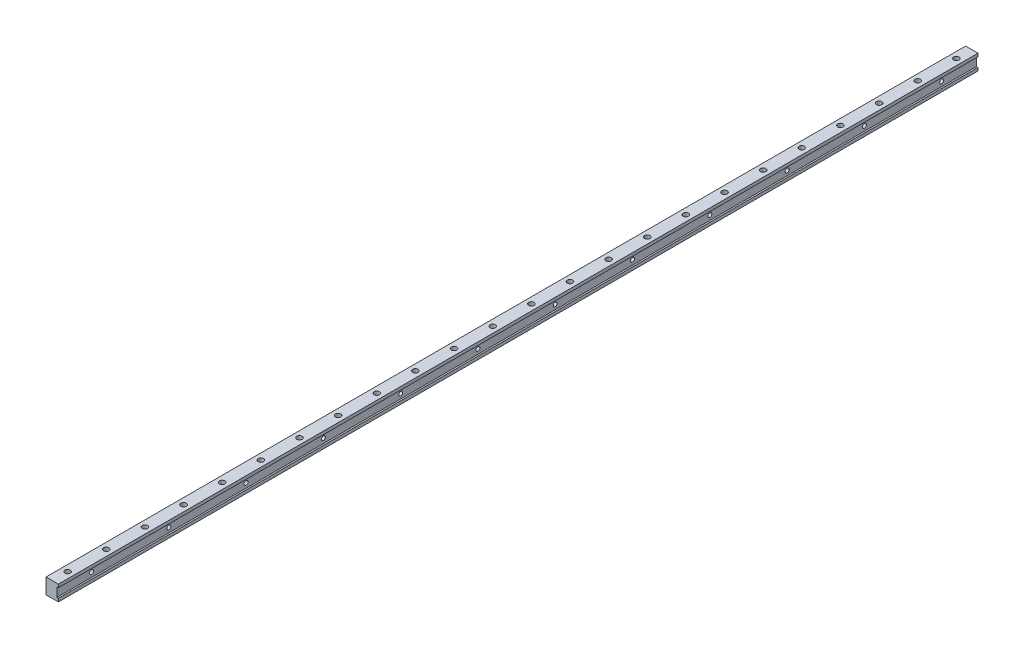
SolidWorks part; units mm, degrees
ref_plane "Front Plane" through (0, 0, 0) normal (0, 0, 1) x (1, 0, 0)
ref_plane "Top Plane" through (0, 0, 0) normal (0, 1, 0) x (1, 0, 0)
ref_plane "Right Plane" through (0, 0, 0) normal (1, 0, 0) x (0, 0, -1)
sketch "Sketch1" plane through (0, 0, 0) normal (0, 0, 1) x (1, 0, 0)
  line L1 (-4, -5) -> (4, -5)
  line L2 (-4, -5) -> (-4, 5)
  line L3 (-4, 5) -> (4, 5)
  line L4 (4, -5) -> (4, 5)
  line L5 (-4, -5) -> (4, 5) construction
  line L6 (-4, 5) -> (4, -5) construction
  point P0 (0, 0)
  dimension "D1" = 8
  dimension "D2" = 10
extrude "Boss-Extrude1" add sketch "Sketch1" along normal blind 595
sketch "Sketch2" plane through (0, 5, 0) normal (0, 1, 0) x (1, 0, 0)
  line L0 (4, 0) -> (-4, 0) construction
  circle A0 centre (0, -10) radius 1.75
  dimension "D2" = 3.5
  dimension "D1" = 10
extrude "Cut-Extrude1" cut sketch "Sketch2" against normal through all
pattern_linear "LPattern1" count 24 spacing 25 along (0, 0, 1) of "Cut-Extrude1"
sketch "Sketch3" plane through (-4, 0, 0) normal (-1, 0, 0) x (0, 0, 1)
  line L0 (0, 0) -> (595, 0) construction
  line L1 (595, 5) -> (595, -5) construction
  line L2 (0, 5) -> (0, -5) construction
  circle A0 centre (22.5, 0) radius 1.3
  dimension "D1" = 2.6
  dimension "D2" = 22.5
extrude "Cut-Extrude2" cut sketch "Sketch3" against normal through all
pattern_linear "LPattern2" count 12 spacing 50 along (0, 0, 1) of "Cut-Extrude2"
sketch "Sketch4" plane through (0, 0, 0) normal (0, 0, -1) x (-1, 0, 0)
  line L1 (-4, 0) -> (4, 0) construction
  line L2 (-4, -5) -> (-4, 5) construction
  line L3 (4, 5) -> (4, -5) construction
  line L4 (-4, -3) -> (-3, -3)
  line L5 (-4, 3) -> (-3, 3)
  line L6 (-3, -3) -> (-3, 3)
  line L7 (-4, -3) -> (-4, 3)
  dimension "D1" = 6
  dimension "D2" = 1
extrude "Cut-Extrude3" cut sketch "Sketch4" against normal through all
